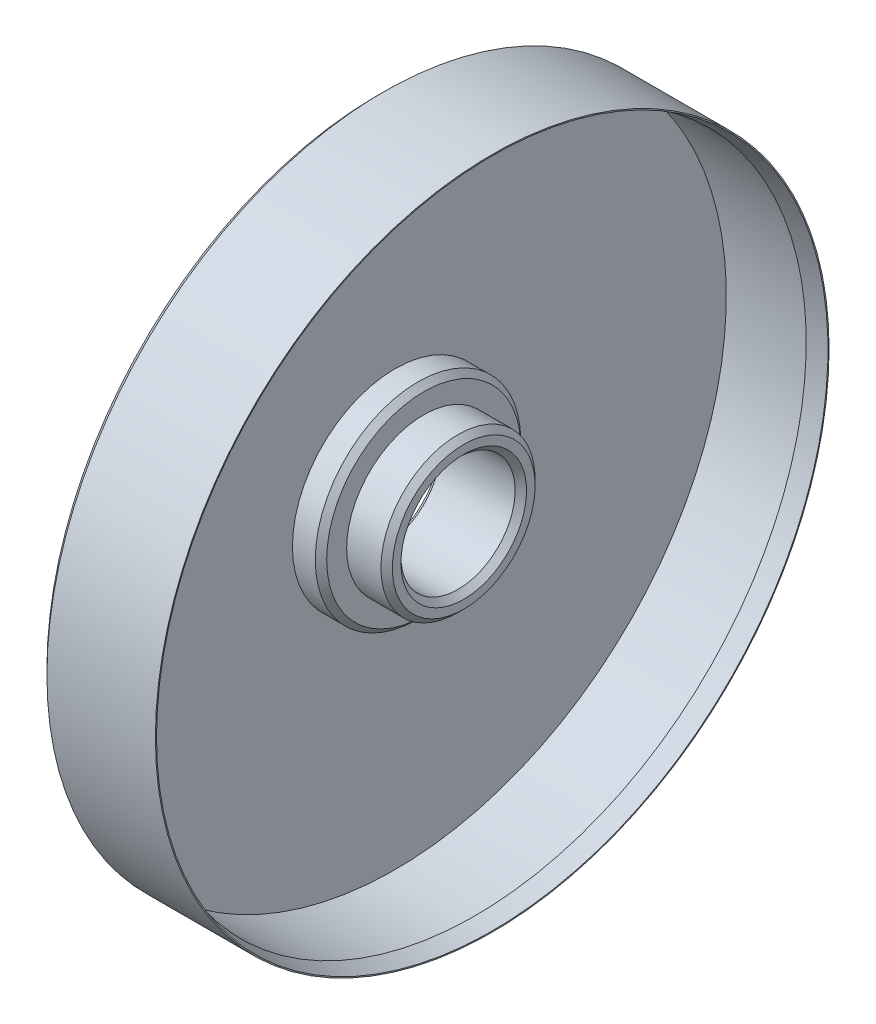
SolidWorks part; units mm, degrees
ref_plane "Спереди" through (0, 0, 0) normal (0, 0, 1) x (1, 0, 0)
ref_plane "Сверху" through (0, 0, 0) normal (0, 1, 0) x (1, 0, 0)
ref_plane "Справа" through (0, 0, 0) normal (1, 0, 0) x (0, 0, -1)
other "Configuration Table"
sketch "Эскиз1" plane through (0, 0, 0) normal (0, 0, 1) x (1, 0, 0)
  line L0 (0, 0) -> (36, 0) construction
  line L1 (0, 11) -> (0, 58)
  line L2 (1, 59) -> (20, 59)
  line L3 (20, 59) -> (20, 58.8038)
  line L4 (20, 58.8038) -> (17, 58)
  line L5 (17, 58) -> (3, 58)
  line L6 (3, 58) -> (3, 18)
  line L7 (8, 13.5) -> (14, 13.5)
  line L8 (15, 12.5) -> (15, 11)
  line L9 (14, 10) -> (1, 10)
  line L10 (3, 18) -> (7, 18)
  line L11 (8, 17) -> (8, 13.5)
  line L12 (1, 10) -> (0, 11)
  line L13 (15, 11) -> (14, 10)
  line L14 (14, 13.5) -> (15, 12.5)
  line L15 (7, 18) -> (8, 17)
  line L16 (0, 58) -> (1, 59)
  point P3 (0, 10)
  point P4 (0, 59)
  point P11 (15, 13.5)
  point P12 (15, 10)
  point P13 (8, 18)
  dimension "D1" = 20
  dimension "D2" = 15
  dimension "D3" = 3
  dimension "D4" = 27
  dimension "D5" = 5
  dimension "D6" = 36
  dimension "D7" = 20
  dimension "D8" = 15
  dimension "D9" = 1
  dimension "D10" = 118
  dimension "D11" = 3
revolve "Повернуть1" add sketch "Эскиз1" angle 360 about L0
